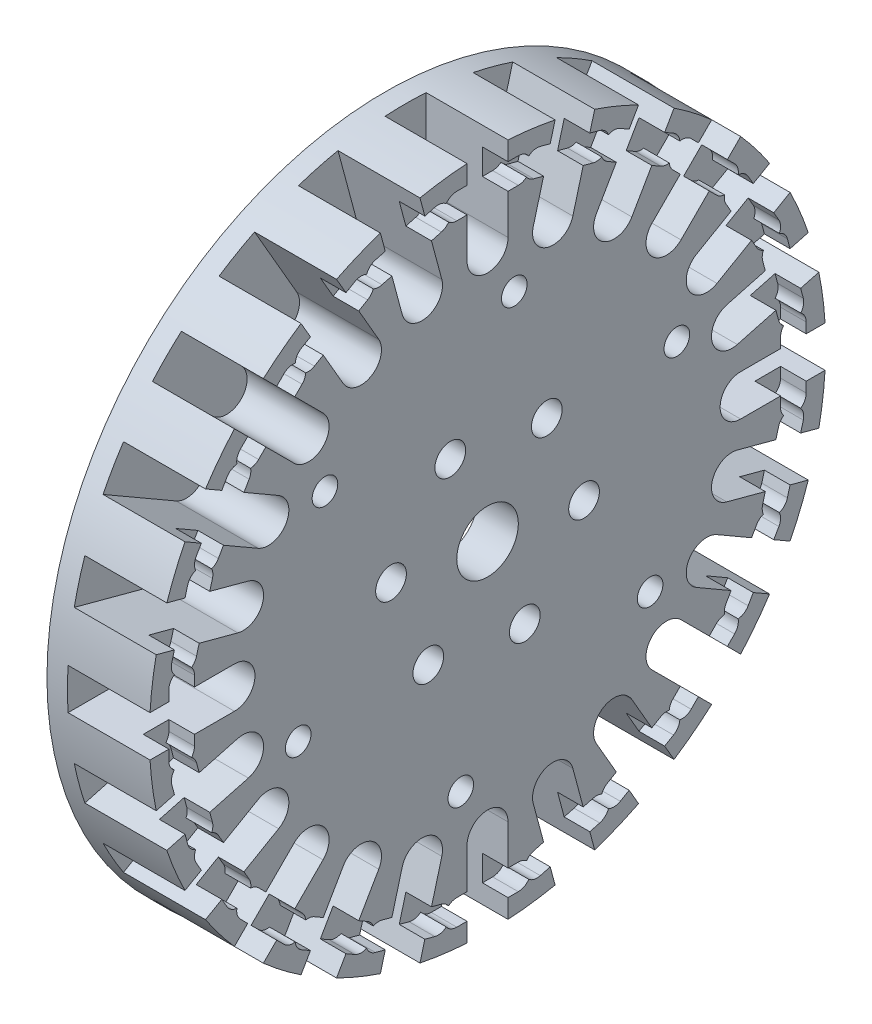
SolidWorks part; units mm, degrees
ref_plane "Front Plane" through (0, 0, 0) normal (0, 0, 1) x (1, 0, 0)
ref_plane "Top Plane" through (0, 0, 0) normal (0, 1, 0) x (1, 0, 0)
ref_plane "Right Plane" through (0, 0, 0) normal (1, 0, 0) x (0, 0, -1)
sketch "Sketch1" plane through (0, 0, 0) normal (1, 0, 0) x (0, 0, -1)
  circle A0 centre (0, 0) radius 33
  circle A1 centre (0, 0) radius 3.005
  dimension "D1" = 66
  dimension "D2" = 6.01
extrude "Boss-Extrude1" add sketch "Sketch1" along normal blind 10
sketch "Sketch2" plane through (10, 0, 0) normal (1, 0, 0) x (0, 0, -1)
  line L0 (-2, 33) -> (2, 33)
  line L1 (2, 33) -> (2, 24.7)
  line L2 (-2, 24.7) -> (-2, 33)
  arc A0 (2, 24.7) -> (-2, 24.7) centre (0, 24.7) cw
  circle A1 centre (0, 0) radius 33 construction
  dimension "D1" = 4
  dimension "D2" = 8.3
extrude "Cut-Extrude1" cut sketch "Sketch2" against normal blind 8
sketch "Sketch3" plane through (10, 0, 0) normal (1, 0, 0) x (0, 0, -1)
  line L0 (-3, 29.85) -> (3, 29.85) construction
  line L1 (-3, 31.1) -> (3, 31.1)
  line L2 (-3, 28.6) -> (3, 28.6)
  arc A0 (-3, 31.1) -> (-3, 28.6) centre (-3, 29.85) ccw
  arc A1 (3, 28.6) -> (3, 31.1) centre (3, 29.85) ccw
  arc A2 (-2, 24.7) -> (2, 24.7) centre (0, 24.7) ccw construction
  point P2 (0, 29.85)
  dimension "D1" = 1.25
  dimension "D2" = 5.15
  dimension "D3" = 6
extrude "Cut-Extrude2" cut sketch "Sketch3" against normal blind 2.5
pattern_circular "CirPattern1" count 24 over 360 about axis through (10, 0, 0) along (1, 0, 0) of "Cut-Extrude1", "Cut-Extrude2"
hole_wizard "Tap Drill for M3x0.5 Tap1" positions "Sketch6" profile "Sketch5" hole size "M3x0.5" standard "ANSI Metric" end condition up to next
sketch "Sketch6" plane through (10, 0, 0) normal (1, 0, 0) x (0, 0, -1)
  line L0 (2.6105, 19.8289) -> (0, 0) construction
  line L1 (0, 0) -> (3.005, 0) construction
  circle A2 centre (0, 0) radius 3.005 construction
  point P0 (2.6105, 19.8289)
  dimension "D1" = 82.5
  dimension "D2" = 20
sketch "Sketch5" plane through (10, 19.8289, -2.6105) normal (0, 1, 0) x (0, 0, -1)
  line L0 (0, 0) -> (0, 10.001)
  line L1 (0, 10.001) -> (1.25, 10.001)
  line L2 (1.25, 10.001) -> (1.25, 0)
  line L5 (1.25, 0) -> (0, 0)
  line L11 (0, -6.35) -> (0, 107.95) construction
  dimension "Thru Hole Dia." = 2.5
  dimension "Thru Hole Depth" = 10.001
pattern_circular "CirPattern2" count 6 over 360 about axis through (10, 0, 0) along (1, 0, 0) of "Tap Drill for M3x0.5 Tap1"
sketch "Sketch7" plane through (0, 0, 0) normal (-1, 0, 0) x (0, 0, 1)
  circle A0 centre (0, 0) radius 12.71
  dimension "D1" = 25.42
extrude "Cut-Extrude3" cut sketch "Sketch7" against normal blind 6
sketch "Sketch11" plane through (10, 0, 0) normal (1, 0, 0) x (0, 0, -1)
  line L0 (0, 0) -> (-10.5081, 0) construction
  line L1 (-3.6355, 8.7769) -> (0, 0) construction
  circle A0 centre (-3.6355, 8.7769) radius 1.5
  dimension "D1" = 3
  dimension "D2" = 9.5
  dimension "D3" = 67.5
extrude "Cut-Extrude4" cut sketch "Sketch11" against normal up to next
pattern_circular "CirPattern3" count 6 over 360 about axis through (10, 0, 0) along (1, 0, 0) of "Cut-Extrude4"
